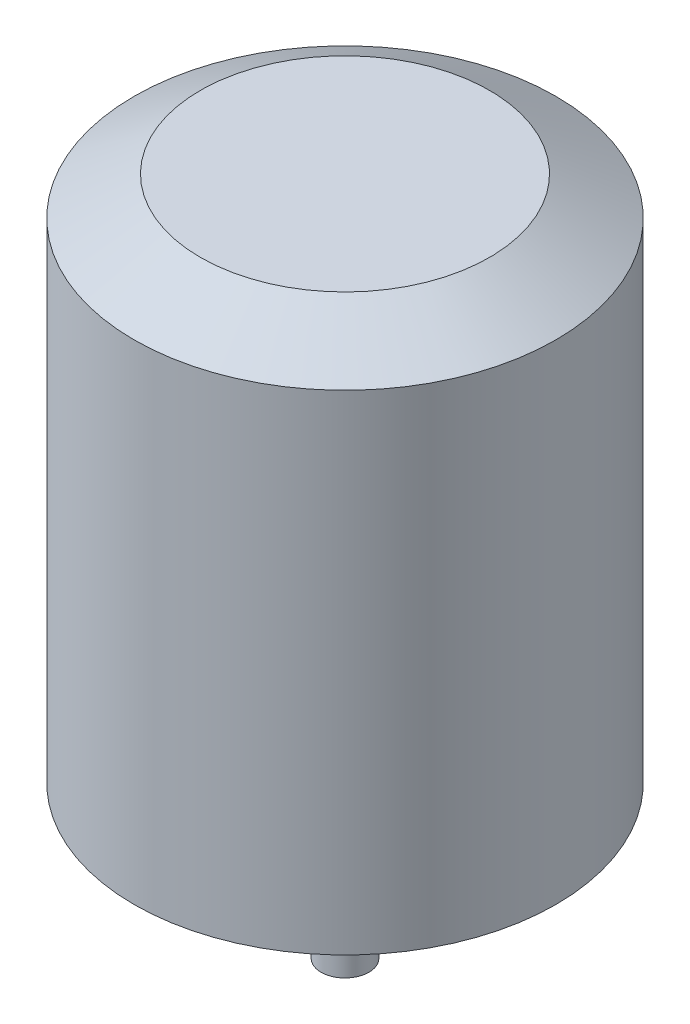
SolidWorks part; units mm, degrees
ref_plane "Front Plane" through (0, 0, 0) normal (0, 0, 1) x (1, 0, 0)
ref_plane "Top Plane" through (0, 0, 0) normal (0, 1, 0) x (1, 0, 0)
ref_plane "Right Plane" through (0, 0, 0) normal (1, 0, 0) x (0, 0, -1)
other "Bounding Box"
ref_plane "Default Plane" through (-8.9266, -12.7485, 0) normal (-0.1736, 0.9848, 0) x (0.9848, 0.1736, 0)
sketch "Sketch1" plane through (0, 0, 0) normal (0, 1, 0) x (1, 0, 0)
  circle A0 centre (0, 0) radius 14
  dimension "D1" = 28
extrude "Boss-Extrude1" add sketch "Sketch1" along normal mid plane 35
chamfer "Chamfer1" distance 2.54 angle 60 1 edges at (0, 17.5, 14) first distance on face at (0, 17.5, 14)
sketch "Sketch2" plane through (0, -17.5, 0) normal (0, -1, 0) x (1, 0, 0)
  circle A0 centre (0, 0) radius 1.5875
  dimension "D1" = 3.175
extrude "Boss-Extrude2" add sketch "Sketch2" along normal offset from surface (10.1 mm away) 45.1 up to face at (0, 17.5, 9.6006)
